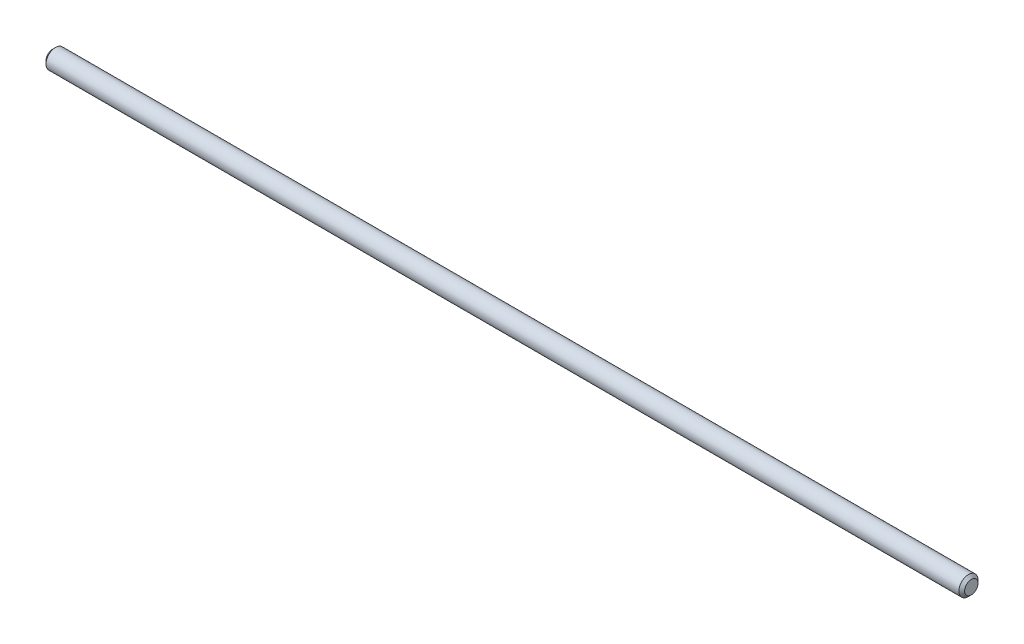
SolidWorks part; units mm, degrees
material "6061 Alloy"
ref_plane "Front Plane" through (0, 0, 0) normal (0, 0, 1) x (1, 0, 0)
ref_plane "Top Plane" through (0, 0, 0) normal (0, 1, 0) x (1, 0, 0)
ref_plane "Right Plane" through (0, 0, 0) normal (1, 0, 0) x (0, 0, -1)
sketch "Sketch1" plane through (0, 0, 0) normal (0, 0, 1) x (1, 0, 0)
  line L0 (-152.4, 0) -> (152.4, 0) construction
  line L1 (152.4, 3.175) -> (152.4, -3.175) construction
  line L2 (-152.4, 3.175) -> (-152.4, -3.175) construction
  line L3 (152.4, 3.175) -> (69.85, 3.175) construction
  point P6 (147.955, -3.175)
  point P9 (-139.7, 0)
  point P10 (139.7, 0)
  point P11 (-114.3, 0)
  point P12 (114.3, 0)
  dimension "D1" = 4.445
  dimension "D2" = 12.7
  dimension "D3" = 12.7
  dimension "D4" = 25.4
  dimension "D5" = 25.4
sketch "Sketch2" plane through (0, 0, 0) normal (1, 0, 0) x (0, 0, -1)
  circle A0 centre (0, 0) radius 3.175
extrude "Boss-Extrude1" add sketch "Sketch2" against normal up to vertex (152.4 mm away) and the other way up to vertex (152.4 mm away) up to point (-152.4, 0, 0) other way up to point (152.4, 0, 0)
chamfer "Chamfer1" distance 0.9525 angle 45 2 edges at (-152.4, 0, -3.175) (152.4, 0, -3.175)
sketch "Drawing1" plane through (0, 0, 0) normal (1, 0, 0) x (0, 0, -1)
  circle A0 centre (0, 0) radius 3.175
sketch "Sketch3" [suppressed] plane through (304.8, 0, 0) normal (1, 0, 0) x (0, 0, -1)
  circle A1 centre (0, 0) radius 3.175
  circle A2 centre (0, 0) radius 3.175
  dimension "D1" = 0
curve "Helix/Spiral1" [suppressed] pitch 1.27 height 83.82 turns 66 parameters "Pitch"=1.27
sketch "Sketch4" [suppressed] plane through (0, 0, 0) normal (0, 0, 1) x (1, 0, 0)
  line L0 (305.3556, 2.3501) -> (305.3556, 3.175) construction
  line L1 (305.0381, 2.7626) -> (305.6731, 2.7626) construction
  line L2 (304.3237, 3.9999) -> (305.2763, 2.3501)
  line L3 (306.3875, 3.9999) -> (305.435, 2.3501)
  line L4 (304.3237, 3.9999) -> (306.3875, 3.9999)
  line L5 (305.2763, 2.3501) -> (305.435, 2.3501) construction
  line L7 (305.2763, 2.3501) -> (304.8, 3.175) construction
  line L8 (305.2763, 2.3501) -> (305.435, 2.3501)
  line L9 (304.8, 3.175) -> (305.9113, 3.175) construction
  line L10 (305.9113, 3.175) -> (305.435, 2.3501) construction
  point P9 (304.8, 3.175)
  point P11 (305.9113, 3.175)
  dimension "D2" = 0.1588
  dimension "D1" = 0.635
  dimension "D3" = 60
sweep "Cut-Sweep3" [suppressed] cut profiles "Sketch4" path "Helix/Spiral1"
pattern_linear "LPattern1" [suppressed] count 5 spacing 81.28 along (-1, 0, 0) of bodies 102
ref_plane "Plane1" [suppressed] through (-266.7, 0, 0) normal (1, 0, 0) x (0, 0, -1)
ref_plane "Plane2" [suppressed] through (266.7, 0, 0) normal (1, 0, 0) x (0, 0, -1)
split "Split1" [suppressed] bodies to split 103
equation "\"D3@Helix/Spiral1\"=\"Pitch@Helix/Spiral1\"+\"Segment Length@Sketch1\""
equation "\"D1@Chamfer1\" = \"Pitch@Helix/Spiral1\"*.75"
equation "\"D2@Sketch4\"=\"Pitch@Helix/Spiral1\"*.125"
equation "\"D1@Sketch1\" = \"Pitch@Helix/Spiral1\"*3.50"
equation "\"Segment Length@Sketch1\" = \"Pitch@Helix/Spiral1\"*65"
equation "\"D1@LPattern1\"=(\"Length@Sketch1\"/(\"Segment Length@Sketch1\"-\"Pitch@Helix/Spiral1\"))+1"
equation "\"D3@LPattern1\"=\"Segment Length@Sketch1\"-\"Pitch@Helix/Spiral1\""
equation "\"D2@Sketch1\"=\"Thread Diameter@Sketch1\"*2"
equation "\"D3@Sketch1\"=\"Thread Diameter@Sketch1\"*2"
equation "\"D1@Sketch4\"=\"Pitch@Helix/Spiral1\"*.5"
